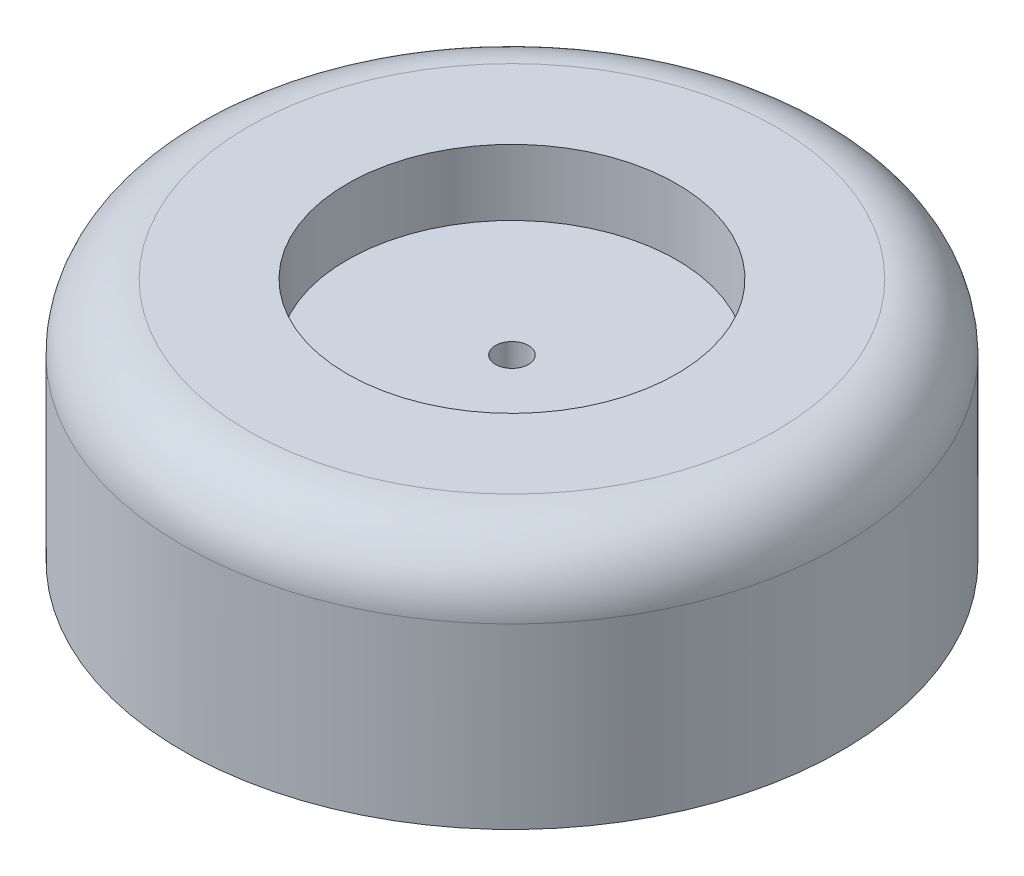
SolidWorks part; units mm, degrees
ref_plane "Front Plane" through (0, 0, 0) normal (0, 0, 1) x (1, 0, 0)
ref_plane "Top Plane" through (0, 0, 0) normal (0, 1, 0) x (1, 0, 0)
ref_plane "Right Plane" through (0, 0, 0) normal (1, 0, 0) x (0, 0, -1)
sketch "Sketch1" plane through (0, 0, 0) normal (0, 1, 0) x (1, 0, 0)
  circle A0 centre (0, 0) radius 47.5
  circle A1 centre (0, 0) radius 50
  dimension "Flange Outer Diameter" = 95
  dimension "Flange Main thickness" = 2.5
extrude "Boss-Extrude1" add sketch "Sketch1" along normal blind 10
sketch "Sketch2" plane through (0, 10, 0) normal (0, 1, 0) x (1, 0, 0)
  circle A0 centre (0, 0) radius 50 construction
  circle A1 centre (0, 0) radius 50
extrude "Boss-Extrude2" add sketch "Sketch2" along normal blind 30
sketch "Sketch3" plane through (0, 10, 0) normal (0, -1, 0) x (1, 0, 0)
  circle A0 centre (0, 0) radius 42.5
  dimension "Bearing track diameter" = 85
sketch "Sketch4" plane through (0, 0, 0) normal (0, 0, 1) x (1, 0, 0)
  line L0 (0, 0) -> (0, 10) construction
  line L1 (-42.5, 10) -> (42.5, 10) construction
  line L2 (0, 10) -> (42.5, 10) construction
  circle A0 centre (42.5, 10) radius 2.5
  dimension "Bearing Ball OD" = 5
  dimension "Bearing track radius" = 42.5
sweep "Cut-Sweep1" cut profiles "Sketch4" path "Sketch3"
sketch "Sketch5" plane through (0, 10, 0) normal (0, -1, 0) x (1, 0, 0)
  circle A0 centre (0, 0) radius 47.5 construction
  circle A1 centre (0, 0) radius 47.5
sketch "Sketch6" plane through (0, 0, 0) normal (0, -1, 0) x (1, 0, 0)
  circle A0 centre (0, 0) radius 50 construction
  circle A1 centre (0, 0) radius 50
extrude "Cut-Extrude2" cut sketch "Sketch6" against normal blind 3
sketch "Sketch7" plane through (0, 40, 0) normal (0, 1, 0) x (1, 0, 0)
  circle A0 centre (0, 0) radius 2.5
  dimension "Center Bolt OD" = 5
extrude "Cut-Extrude3" cut sketch "Sketch7" against normal through all and the other way through all
fillet "Fillet1" radius 10 1 edges at (0, 40, 50)
sketch "Sketch9" plane through (0, 40, 0) normal (0, 1, 0) x (1, 0, 0)
  circle A0 centre (0, 0) radius 25
  dimension "Flange attachment hole" = 50
extrude "Cut-Extrude5" cut sketch "Sketch9" against normal blind 10
sketch "Sketch10" plane through (0, 10, 0) normal (0, -1, 0) x (1, 0, 0)
  circle A0 centre (0, 0) radius 15
  circle A1 centre (0, 0) radius 22
  dimension "Magnet ID" = 30
  dimension "Magnet OD Difference" = 7
extrude "Cut-Extrude6" cut sketch "Sketch10" against normal blind 4
